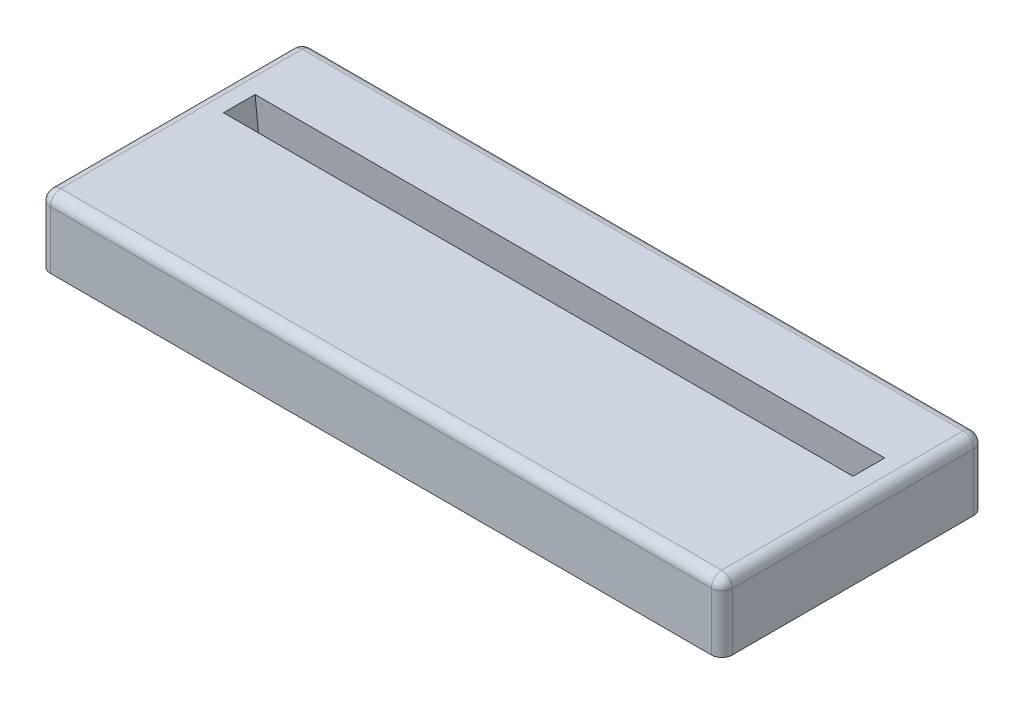
SolidWorks part; units mm, degrees
ref_plane "Přední rovina" through (0, 0, 0) normal (0, 0, 1) x (1, 0, 0)
ref_plane "Horní rovina" through (0, 0, 0) normal (0, 1, 0) x (1, 0, 0)
ref_plane "Pravá rovina" through (0, 0, 0) normal (1, 0, 0) x (0, 0, -1)
sketch "Skica8" plane through (0, 0, 0) normal (1, 0, 0) x (0, 0, -1)
  line L0 (4.9589, 7.0228) -> (6, -3.9278)
  line L1 (-25, 6.5) -> (25, 6.5)
  line L2 (-25, 6.5) -> (-25, -6.5)
  line L3 (-25, -6.5) -> (25, -6.5)
  line L4 (25, 6.5) -> (25, -6.5)
  line L5 (-25, 6.5) -> (25, -6.5) construction
  line L6 (-25, -6.5) -> (25, 6.5) construction
  line L11 (4.9589, 7.0228) -> (10.932, 7.5907)
  line L12 (7.5, -6.5) -> (10.5, -3.5) construction
  line L13 (7.5, -6.5) -> (10.5, -6.5)
  line L14 (7.5, -6.5) -> (7.5, -3.7852)
  line L15 (7.5, -3.7852) -> (10.5, -3.5)
  line L16 (10.5, -6.5) -> (10.5, -3.5)
  line L17 (7.5, -3.7852) -> (10.5, -6.5) construction
  line L18 (6, -3.9278) -> (11.9731, -3.36)
  line L19 (10.932, 7.5907) -> (11.9731, -3.36)
  line L20 (6, -3.9278) -> (10.932, 7.5907) construction
  line L21 (4.9589, 7.0228) -> (11.9731, -3.36) construction
  point P0 (0, 0)
  point P6 (0, 0)
  point P9 (0, 0)
  point P15 (9, -5)
  point P17 (0, 0)
  point P18 (0, 0)
  point P19 (0, 0)
  dimension "D1" = 13
  dimension "D2" = 50
  dimension "D3" = 6
  dimension "D4" = 11
  dimension "D5" = 3
  dimension "D6" = 1.5
  dimension "D7" = 16
extrude "Přidat vysunutím10" add sketch "Skica8" along normal blind 120 contours L16 L3 L4 L1 L0 | L3 L14 L0 L1 L2 region at (0, -0.09, 9.5347) region at (0, -0.0426, -18.1263)
extrude "Přidat vysunutím11" add sketch "Skica8<3>" against normal blind 5 contours L3 L14 L0 L1 L2 | L1 L0 | L16 L3 L4 L1 L0 | L3 L16 L0 L14 region at (0, 1.4267, -8.4763) region at (0, -0.09, 9.5347) region at (0, -0.0426, -18.1263) region at (0, -5.0701, -9.025)
sketch "Skica8<3>" plane through (0, 0, 0) normal (1, 0, 0) x (0, 0, -1) same geometry as "Skica8"
sketch "Skica12" plane through (120, 0, 0) normal (1, 0, 0) x (0, 0, -1)
  line L1 (-25, -6.5) -> (25, -6.5)
  line L2 (-25, -6.5) -> (-25, 6.5)
  line L3 (-25, 6.5) -> (25, 6.5)
  line L4 (25, -6.5) -> (25, 6.5)
  line L5 (-25, -6.5) -> (25, 6.5) construction
  line L6 (-25, 6.5) -> (25, -6.5) construction
  point P0 (0, 0)
extrude "Přidat vysunutím13" add sketch "Skica12" along normal blind 5
sketch "Skica13" plane through (0, -6.5, 0) normal (0, -1, 0) x (1, 0, 0)
  line L0 (-5, 25) -> (-5, -25) construction
  line L1 (-3.1, 23.1) -> (123.1, 23.1)
  line L2 (-3.1, 23.1) -> (-3.1, -23.1)
  line L3 (-3.1, -23.1) -> (123.1, -23.1)
  line L4 (123.1, 23.1) -> (123.1, -23.1)
  line L5 (125, 25) -> (125, -25) construction
  line L6 (-5, 25) -> (125, 25) construction
  line L7 (125, -25) -> (-5, -25) construction
  line L9 (-1.9, 21.9) -> (121.9, 21.9)
  line L10 (-1.9, 21.9) -> (-1.9, -21.9)
  line L11 (-1.9, -21.9) -> (121.9, -21.9)
  line L12 (121.9, 21.9) -> (121.9, -21.9)
  dimension "D1" = 1.9
  dimension "D2" = 1.9
  dimension "D3" = 1.9
  dimension "D4" = 1.9
  dimension "D5" = 1.2
  dimension "D6" = 1.2
  dimension "D7" = 1.2
  dimension "D8" = 1.2
extrude "Odebrat vysunutím1" cut sketch "Skica13" against normal blind 7
fillet "Zaoblit2" radius 2 8 edges at (-5, 6.5, 0) (60, 6.5, -25) (125, 6.5, 0) (60, 6.5, 25) (125, 0, 25) (-5, 0, 25) (-5, 0, -25) (125, 0, -25)
